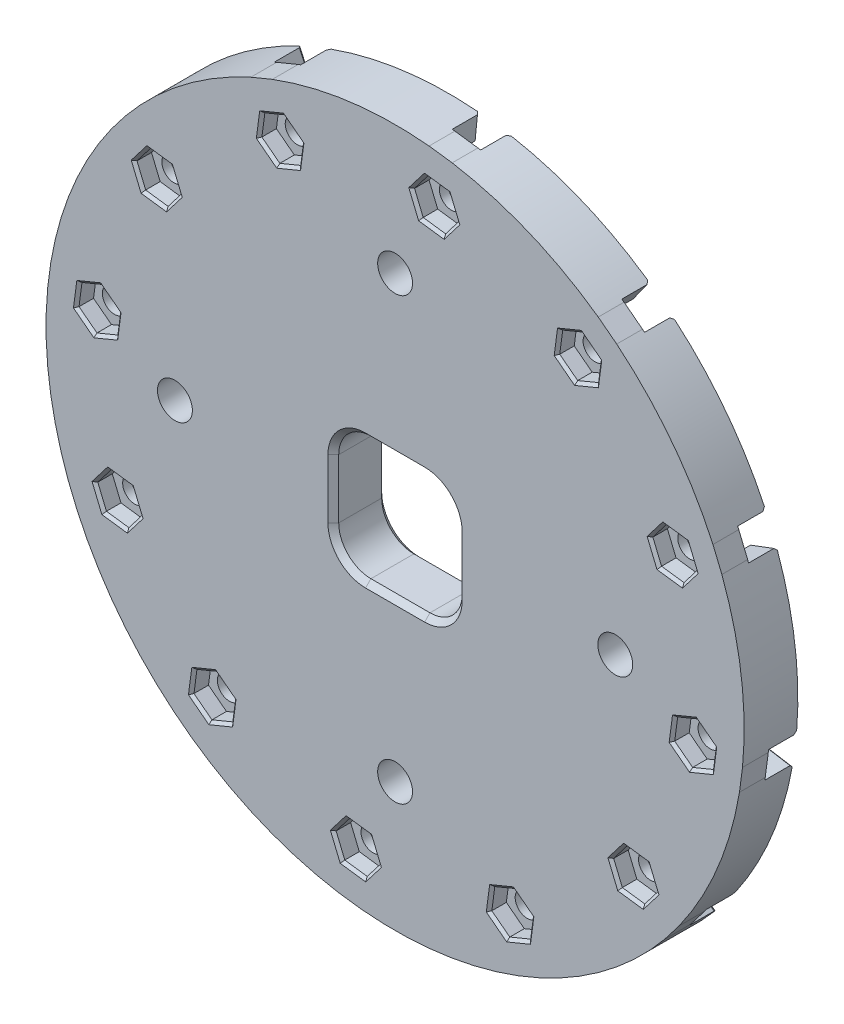
SolidWorks part; units mm, degrees
note: The reader was unsure of these and kept them because the rebuilt part matched: shared geometry of "Sketch4<7>".
material "ABS"
ref_plane "Front" through (0, 0, 0) normal (0, 0, 1) x (1, 0, 0)
ref_plane "Top" through (0, 0, 0) normal (0, 1, 0) x (1, 0, 0)
ref_plane "Right" through (0, 0, 0) normal (1, 0, 0) x (0, 0, -1)
sketch "Sketch1" plane through (0, 0, 0) normal (0, 0, 1) x (1, 0, 0)
  line L0 (-125.5954, 5.9057) -> (-58.2664, 51.1954)
  line L1 (-125.5954, -5.9057) -> (-58.2664, -51.1954)
  line L2 (0, 216.5) -> (0, -216.5) construction
  line L3 (-112.5, 5) -> (-102.5, 5)
  line L4 (-112.5, 5) -> (-112.5, -5)
  line L5 (-112.5, -5) -> (-102.5, -5)
  line L6 (-102.5, 5) -> (-102.5, -5)
  line L7 (-112.5, 5) -> (-102.5, -5) construction
  line L8 (-112.5, -5) -> (-102.5, 5) construction
  line L9 (216.5, 0) -> (-216.5, 0) construction
  line L10 (0, 0) -> (-153.0886, 153.0886) construction
  line L11 (0, 0) -> (153.0886, 153.0886) construction
  line L12 (0, 0) -> (153.0886, -153.0886) construction
  line L13 (0, 0) -> (-153.0886, -153.0886) construction
  line L14 (-5, 196.4364) -> (-5, 145.6348)
  line L15 (5, 196.4364) -> (5, 145.6348)
  line L16 (-5, -74.8331) -> (-5, -125.6348)
  line L17 (5, -74.8331) -> (5, -125.6348)
  line L18 (74.8331, 5) -> (125.6348, 5)
  line L19 (74.8331, -5) -> (125.6348, -5)
  line L22 (-142.437, 135.366) -> (-106.5149, 99.4438)
  line L23 (-49.8116, 56.8826) -> (-85.3017, 92.3727)
  line L24 (-49.8116, 56.8826) -> (-41.8605, 62.231)
  line L25 (-58.2664, -51.1954) -> (-92.3727, -85.3017)
  line L26 (-135.366, -142.437) -> (-99.4438, -106.5149)
  line L27 (-49.8116, -56.8826) -> (-41.8605, -62.231)
  line L28 (49.3795, -56.4506) -> (85.3017, -92.3727)
  line L29 (56.4506, -49.3795) -> (92.3727, -85.3017)
  line L30 (142.437, 135.366) -> (106.5149, 99.4438)
  line L31 (135.366, 142.437) -> (99.4438, 106.5149)
  line L32 (85.3017, 92.3727) -> (49.3795, 56.4506)
  line L33 (-11.5, 11.5) -> (11.5, 11.5)
  line L34 (-11.5, 11.5) -> (-11.5, -11.5)
  line L35 (-11.5, -11.5) -> (11.5, -11.5)
  line L36 (11.5, 11.5) -> (11.5, -11.5)
  line L37 (-11.5, 11.5) -> (11.5, -11.5) construction
  line L38 (-11.5, -11.5) -> (11.5, 11.5) construction
  line L39 (92.3727, 85.3017) -> (56.4506, 49.3795)
  line L40 (5, 125.6348) -> (5, 74.8331)
  line L41 (-5, 125.6348) -> (-5, 74.8331)
  line L42 (145.6348, 5) -> (196.4364, 5)
  line L43 (145.6348, -5) -> (196.4364, -5)
  line L44 (-99.4438, 106.5149) -> (-135.366, 142.437)
  line L45 (-92.3727, 85.3017) -> (-58.2664, 51.1954)
  line L46 (-145.6348, 5) -> (-196.4364, 5)
  line L47 (-145.6348, -5) -> (-196.4364, -5)
  line L48 (-106.5149, -99.4438) -> (-142.437, -135.366)
  line L49 (-85.3017, -92.3727) -> (-49.8116, -56.8826)
  line L50 (-5, -145.6348) -> (-5, -196.4364)
  line L51 (5, -145.6348) -> (5, -196.4364)
  line L52 (99.4438, -106.5149) -> (135.366, -142.437)
  line L53 (106.5149, -99.4438) -> (142.437, -135.366)
  line L54 (125.6348, 5) -> (145.6348, 5) construction
  line L55 (135.6348, 5) -> (135.6348, 23.3446) construction
  line L56 (74.8331, 2.5) -> (196.4364, 2.5) construction
  arc A0 (-41.8605, -62.231) -> (-5, -74.8331) centre (0, 0) ccw
  arc A2 (5, -74.8331) -> (49.3795, -56.4506) centre (0, 0) ccw
  circle A3 centre (0, 0) radius 216.5
  arc A4 (-5, 196.4364) -> (-135.366, 142.437) centre (0, 0) ccw
  arc A5 (-5, 74.8331) -> (-41.8605, 62.231) centre (0, 0) ccw
  arc A6 (5, -196.4364) -> (135.366, -142.437) centre (0, 0) ccw
  arc A7 (74.8331, 5) -> (56.4506, 49.3795) centre (0, 0) ccw
  arc A8 (196.4364, 5) -> (142.437, 135.366) centre (0, 0) ccw
  arc A9 (-196.4364, -5) -> (-142.437, -135.366) centre (0, 0) ccw
  arc A11 (-142.437, 135.366) -> (-196.4364, 5) centre (0, 0) ccw
  arc A12 (-135.366, -142.437) -> (-5, -196.4364) centre (0, 0) ccw
  arc A13 (56.4506, -49.3795) -> (74.8331, -5) centre (0, 0) ccw
  arc A14 (142.437, -135.366) -> (196.4364, -5) centre (0, 0) ccw
  arc A15 (49.3795, 56.4506) -> (5, 74.8331) centre (0, 0) ccw
  arc A16 (135.366, 142.437) -> (5, 196.4364) centre (0, 0) ccw
  circle A17 centre (0, 41) radius 3.25
  circle A18 centre (41, 0) radius 3.25
  circle A19 centre (0, -41) radius 3.25
  circle A20 centre (-41, 0) radius 3.25
  arc A21 (85.3017, 92.3727) -> (5, 125.6348) centre (0, 0) ccw
  arc A22 (99.4438, 106.5149) -> (5, 145.6348) centre (0, 0) ccw
  arc A23 (-5, 145.6348) -> (-99.4438, 106.5149) centre (0, 0) ccw
  arc A24 (-5, 125.6348) -> (-85.3017, 92.3727) centre (0, 0) ccw
  arc A25 (125.6348, 5) -> (92.3727, 85.3017) centre (0, 0) ccw
  arc A26 (145.6348, 5) -> (106.5149, 99.4438) centre (0, 0) ccw
  arc A27 (-106.5149, 99.4438) -> (-145.6348, 5) centre (0, 0) ccw
  arc A28 (-92.3727, 85.3017) -> (-125.5954, 5.9057) centre (0, 0) ccw
  arc A29 (-145.6348, -5) -> (-106.5149, -99.4438) centre (0, 0) ccw
  arc A30 (-125.5954, -5.9057) -> (-92.3727, -85.3017) centre (0, 0) ccw
  arc A31 (-85.3017, -92.3727) -> (-5, -125.6348) centre (0, 0) ccw
  arc A32 (-99.4438, -106.5149) -> (-5, -145.6348) centre (0, 0) ccw
  arc A33 (5, -125.6348) -> (85.3017, -92.3727) centre (0, 0) ccw
  arc A34 (5, -145.6348) -> (99.4438, -106.5149) centre (0, 0) ccw
  arc A35 (92.3727, -85.3017) -> (125.6348, -5) centre (0, 0) ccw
  arc A36 (106.5149, -99.4438) -> (145.6348, -5) centre (0, 0) ccw
  point P25 (0, 0)
  point P33 (-107.5, 0)
  point P68 (0, 0)
  point P105 (135.6348, 2.5)
  dimension "D1" = 150
  dimension "D6" = 433
  dimension "D9" = 20
  dimension "D19" = 6.5
  dimension "D3" = 107.5
  dimension "D4" = 10
  dimension "D5" = 10
  dimension "D7" = 45
  dimension "D8" = 4
  dimension "D10" = 5
  dimension "D11" = 10
  dimension "D12" = 5
  dimension "D13" = 10
  dimension "D14" = 10
  dimension "D15" = 10
  dimension "D16" = 10
  dimension "D17" = 10
  dimension "D18" = 23
  dimension "D20" = 29.5
  dimension "D22" = 10
  dimension "D23" = 2.5
  dimension "D24" = 33.927
  dimension "D25" = 33.927
  dimension "D21" = 4
extrude "Boss-Extrude1" add sketch "Sketch1" along normal blind 10
sketch "Sketch3" plane through (0, 0, 0) normal (0, 1, 0) x (1, 0, 0)
  line L0 (-216.5, -10) -> (-221.5, -10)
  line L1 (-221.5, -10) -> (-221.5, 5)
  line L2 (-221.5, 5) -> (-211.5, 5)
  line L3 (-211.5, 5) -> (-211.5, 2)
  line L4 (-211.5, 2) -> (-216.5, 2)
  line L6 (-216.5, 2) -> (-216.5, -10)
  line L7 (216.5, 0) -> (-216.5, 0) construction
  line L8 (0, 88.3927) -> (0, -66.2884) construction
  dimension "D1" = 2
  dimension "D2" = 3
  dimension "D3" = 5
  dimension "D4" = 10
revolve "Revolve1" add sketch "Sketch3" angle 360 about L8
sketch "Sketch4" plane through (0, 0, 10) normal (0, 0, 1) x (1, 0, 0)
  line L0 (-83.9188, 109.3651) -> (-79.952, 112.4089)
  line L1 (84.7644, 204.6393) -> (24.8744, 60.0522)
  line L2 (5, 125.6348) -> (5, 74.8331) construction
  line L3 (-134.8407, 175.7278) -> (-39.5695, 51.568)
  line L4 (-219.605, -28.9116) -> (-64.4439, -8.4842)
  line L5 (39.5695, -51.568) -> (134.8407, -175.7278)
  line L6 (64.4439, 8.4842) -> (219.605, 28.9116)
  line L7 (-24.8744, -60.0522) -> (-84.7644, -204.6393)
  line L8 (24.8744, 60.0522) -> (-24.8744, -60.0522) construction
  line L9 (-26.8634, 59.1892) -> (-24.797, 54.6361)
  line L10 (-24.797, 54.6361) -> (-29.397, 52.9082)
  line L11 (-29.397, 52.9082) -> (-25.5115, 45.9151)
  line L12 (-25.5115, 45.9151) -> (-14.2779, 50.135)
  line L13 (-14.2779, 50.135) -> (-16.4525, 57.7708)
  line L14 (-16.4525, 57.7708) -> (-21.0525, 56.0428)
  line L15 (-21.0525, 56.0428) -> (-22.8577, 60.8484)
  line L16 (-22.8577, 60.8484) -> (0, 0) construction
  line L17 (-26.8634, 59.1892) -> (0, 0) construction
  line L18 (0, 0) -> (-16.4525, 57.7708) construction
  line L19 (-29.397, 52.9082) -> (0, 0) construction
  line L20 (-26.8634, 59.1892) -> (-22.8577, 60.8484)
  line L21 (-24.8606, 60.0188) -> (0, 0) construction
  line L22 (6.3302, 64.691) -> (10.6288, 64.1251)
  line L23 (9.7894, 59.0607) -> (10.6288, 64.1251)
  line L24 (14.6371, 58.2572) -> (9.7894, 59.0607)
  line L25 (12.7024, 50.5571) -> (14.6371, 58.2572)
  line L26 (0.864, 52.5194) -> (12.7024, 50.5571)
  line L27 (0.9955, 60.5183) -> (0.864, 52.5194)
  line L28 (5.8432, 59.7148) -> (0.9955, 60.5183)
  line L29 (6.3302, 64.691) -> (5.8432, 59.7148)
  line L30 (37.8276, 52.859) -> (41.2674, 50.2196)
  line L31 (38.0082, 46.2534) -> (41.2674, 50.2196)
  line L32 (41.8047, 43.1337) -> (38.0082, 46.2534)
  line L33 (36.2792, 37.4326) -> (41.8047, 43.1337)
  line L34 (27.0079, 45.0511) -> (36.2792, 37.4326)
  line L35 (31.1213, 51.9126) -> (27.0079, 45.0511)
  line L36 (34.9178, 48.7929) -> (31.1213, 51.9126)
  line L37 (37.8276, 52.859) -> (34.9178, 48.7929)
  line L38 (59.1892, 26.8634) -> (60.8484, 22.8577)
  line L39 (56.0428, 21.0525) -> (60.8484, 22.8577)
  line L40 (57.7708, 16.4525) -> (56.0428, 21.0525)
  line L41 (50.135, 14.2779) -> (57.7708, 16.4525)
  line L42 (45.9151, 25.5115) -> (50.135, 14.2779)
  line L43 (52.9082, 29.397) -> (45.9151, 25.5115)
  line L44 (54.6361, 24.797) -> (52.9082, 29.397)
  line L45 (59.1892, 26.8634) -> (54.6361, 24.797)
  line L46 (64.691, -6.3302) -> (64.1251, -10.6288)
  line L47 (59.0607, -9.7894) -> (64.1251, -10.6288)
  line L48 (58.2572, -14.6371) -> (59.0607, -9.7894)
  line L49 (50.5571, -12.7024) -> (58.2572, -14.6371)
  line L50 (52.5194, -0.864) -> (50.5571, -12.7024)
  line L51 (60.5183, -0.9955) -> (52.5194, -0.864)
  line L52 (59.7148, -5.8432) -> (60.5183, -0.9955)
  line L53 (64.691, -6.3302) -> (59.7148, -5.8432)
  line L54 (52.859, -37.8276) -> (50.2196, -41.2674)
  line L55 (46.2534, -38.0082) -> (50.2196, -41.2674)
  line L56 (43.1337, -41.8047) -> (46.2534, -38.0082)
  line L57 (37.4326, -36.2792) -> (43.1337, -41.8047)
  line L58 (45.0511, -27.0079) -> (37.4326, -36.2792)
  line L59 (51.9126, -31.1213) -> (45.0511, -27.0079)
  line L60 (48.7929, -34.9178) -> (51.9126, -31.1213)
  line L61 (52.859, -37.8276) -> (48.7929, -34.9178)
  line L62 (26.8634, -59.1892) -> (22.8577, -60.8484)
  line L63 (21.0525, -56.0428) -> (22.8577, -60.8484)
  line L64 (16.4525, -57.7708) -> (21.0525, -56.0428)
  line L65 (14.2779, -50.135) -> (16.4525, -57.7708)
  line L66 (25.5115, -45.9151) -> (14.2779, -50.135)
  line L67 (29.397, -52.9082) -> (25.5115, -45.9151)
  line L68 (24.797, -54.6361) -> (29.397, -52.9082)
  line L69 (26.8634, -59.1892) -> (24.797, -54.6361)
  line L70 (-6.3302, -64.691) -> (-10.6288, -64.1251)
  line L71 (-9.7894, -59.0607) -> (-10.6288, -64.1251)
  line L72 (-14.6371, -58.2572) -> (-9.7894, -59.0607)
  line L73 (-12.7024, -50.5571) -> (-14.6371, -58.2572)
  line L74 (-0.864, -52.5194) -> (-12.7024, -50.5571)
  line L75 (-0.9955, -60.5183) -> (-0.864, -52.5194)
  line L76 (-5.8432, -59.7148) -> (-0.9955, -60.5183)
  line L77 (-6.3302, -64.691) -> (-5.8432, -59.7148)
  line L78 (-37.8276, -52.859) -> (-41.2674, -50.2196)
  line L79 (-38.0082, -46.2534) -> (-41.2674, -50.2196)
  line L80 (-41.8047, -43.1337) -> (-38.0082, -46.2534)
  line L81 (-36.2792, -37.4326) -> (-41.8047, -43.1337)
  line L82 (-27.0079, -45.0511) -> (-36.2792, -37.4326)
  line L83 (-31.1213, -51.9126) -> (-27.0079, -45.0511)
  line L84 (-34.9178, -48.7929) -> (-31.1213, -51.9126)
  line L85 (-37.8276, -52.859) -> (-34.9178, -48.7929)
  line L86 (-59.1892, -26.8634) -> (-60.8484, -22.8577)
  line L87 (-56.0428, -21.0525) -> (-60.8484, -22.8577)
  line L88 (-57.7708, -16.4525) -> (-56.0428, -21.0525)
  line L89 (-50.135, -14.2779) -> (-57.7708, -16.4525)
  line L90 (-45.9151, -25.5115) -> (-50.135, -14.2779)
  line L91 (-52.9082, -29.397) -> (-45.9151, -25.5115)
  line L92 (-54.6361, -24.797) -> (-52.9082, -29.397)
  line L93 (-59.1892, -26.8634) -> (-54.6361, -24.797)
  line L94 (-64.691, 6.3302) -> (-64.1251, 10.6288)
  line L95 (-59.0607, 9.7894) -> (-64.1251, 10.6288)
  line L96 (-58.2572, 14.6371) -> (-59.0607, 9.7894)
  line L97 (-50.5571, 12.7024) -> (-58.2572, 14.6371)
  line L98 (-52.5194, 0.864) -> (-50.5571, 12.7024)
  line L99 (-60.5183, 0.9955) -> (-52.5194, 0.864)
  line L100 (-59.7148, 5.8432) -> (-60.5183, 0.9955)
  line L101 (-64.691, 6.3302) -> (-59.7148, 5.8432)
  line L102 (-52.859, 37.8276) -> (-50.2196, 41.2674)
  line L103 (-46.2534, 38.0082) -> (-50.2196, 41.2674)
  line L104 (-43.1337, 41.8047) -> (-46.2534, 38.0082)
  line L105 (-37.4326, 36.2792) -> (-43.1337, 41.8047)
  line L106 (-45.0511, 27.0079) -> (-37.4326, 36.2792)
  line L107 (-51.9126, 31.1213) -> (-45.0511, 27.0079)
  line L108 (-48.7929, 34.9178) -> (-51.9126, 31.1213)
  line L109 (-52.859, 37.8276) -> (-48.7929, 34.9178)
  line L110 (-128.753, 167.7942) -> (-124.7863, 170.838)
  line L111 (-124.7863, 170.838) -> (-126.9169, 173.6148)
  line L112 (-126.9169, 173.6148) -> (-122.9502, 176.6586)
  line L113 (-122.9502, 176.6586) -> (-115.645, 167.1383)
  line L114 (-115.645, 167.1383) -> (-119.6118, 164.0945)
  line L115 (-119.6118, 164.0945) -> (-121.7425, 166.8713)
  line L116 (-121.7425, 166.8713) -> (-125.7092, 163.8275)
  line L117 (-125.7092, 163.8275) -> (-128.753, 167.7942)
  line L118 (-124.7863, 170.838) -> (-121.7425, 166.8713) construction
  line L119 (-134.8407, 175.7278) -> (-118.7343, 188.0866) construction
  line L120 (79.0241, 190.7811) -> (80.9375, 195.4005)
  line L121 (80.9375, 195.4005) -> (85.5569, 193.4871)
  line L122 (85.5569, 193.4871) -> (86.8963, 196.7207)
  line L123 (86.8963, 196.7207) -> (91.5157, 194.8073)
  line L124 (91.5157, 194.8073) -> (86.9235, 183.7207)
  line L125 (86.9235, 183.7207) -> (82.3041, 185.6341)
  line L126 (82.3041, 185.6341) -> (83.6435, 188.8677)
  line L127 (83.6435, 188.8677) -> (79.0241, 190.7811)
  line L128 (204.7334, 26.9537) -> (209.6906, 27.6063)
  line L129 (209.6906, 27.6063) -> (210.3432, 22.6491)
  line L130 (210.3432, 22.6491) -> (213.8133, 23.1059)
  line L131 (213.8133, 23.1059) -> (214.4659, 18.1487)
  line L132 (214.4659, 18.1487) -> (202.5686, 16.5824)
  line L133 (202.5686, 16.5824) -> (201.9159, 21.5396)
  line L134 (201.9159, 21.5396) -> (205.386, 21.9964)
  line L135 (205.386, 21.9964) -> (204.7334, 26.9537)
  line L136 (125.7092, -163.8275) -> (128.753, -167.7942)
  line L137 (128.753, -167.7942) -> (124.7863, -170.838)
  line L138 (124.7863, -170.838) -> (126.9169, -173.6148)
  line L139 (126.9169, -173.6148) -> (122.9502, -176.6586)
  line L140 (122.9502, -176.6586) -> (115.645, -167.1383)
  line L141 (115.645, -167.1383) -> (119.6118, -164.0945)
  line L142 (119.6118, -164.0945) -> (121.7425, -166.8713)
  line L143 (121.7425, -166.8713) -> (125.7092, -163.8275)
  line L144 (-79.0241, -190.7811) -> (-80.9375, -195.4005)
  line L145 (-80.9375, -195.4005) -> (-85.5569, -193.4871)
  line L146 (-85.5569, -193.4871) -> (-86.8963, -196.7207)
  line L147 (-86.8963, -196.7207) -> (-91.5157, -194.8073)
  line L148 (-91.5157, -194.8073) -> (-86.9235, -183.7207)
  line L149 (-86.9235, -183.7207) -> (-82.3041, -185.6341)
  line L150 (-82.3041, -185.6341) -> (-83.6435, -188.8677)
  line L151 (-83.6435, -188.8677) -> (-79.0241, -190.7811)
  line L152 (-204.7334, -26.9537) -> (-209.6906, -27.6063)
  line L153 (-209.6906, -27.6063) -> (-210.3432, -22.6491)
  line L154 (-210.3432, -22.6491) -> (-213.8133, -23.1059)
  line L155 (-213.8133, -23.1059) -> (-214.4659, -18.1487)
  line L156 (-214.4659, -18.1487) -> (-202.5686, -16.5824)
  line L157 (-202.5686, -16.5824) -> (-201.9159, -21.5396)
  line L158 (-201.9159, -21.5396) -> (-205.386, -21.9964)
  line L159 (-205.386, -21.9964) -> (-204.7334, -26.9537)
  line L160 (-79.952, 112.4089) -> (-82.0827, 115.1856)
  line L161 (-82.0827, 115.1856) -> (-78.1159, 118.2294)
  line L162 (-78.1159, 118.2294) -> (-70.8108, 108.7092)
  line L163 (-70.8108, 108.7092) -> (-74.7775, 105.6654)
  line L164 (-74.7775, 105.6654) -> (-76.9082, 108.4421)
  line L165 (-76.9082, 108.4421) -> (-80.875, 105.3983)
  line L166 (-83.9188, 109.3651) -> (-80.875, 105.3983)
  line L167 (52.7535, 127.3583) -> (50.8401, 122.7389)
  line L168 (55.4595, 120.8255) -> (50.8401, 122.7389)
  line L169 (54.1201, 117.5919) -> (55.4595, 120.8255)
  line L170 (58.7395, 115.6785) -> (54.1201, 117.5919)
  line L171 (63.3317, 126.7651) -> (58.7395, 115.6785)
  line L172 (58.7123, 128.6785) -> (63.3317, 126.7651)
  line L173 (57.3729, 125.4449) -> (58.7123, 128.6785)
  line L174 (52.7535, 127.3583) -> (57.3729, 125.4449)
  line L175 (136.6723, 17.9933) -> (131.7151, 17.3406)
  line L176 (132.3677, 12.3834) -> (131.7151, 17.3406)
  line L177 (128.8977, 11.9266) -> (132.3677, 12.3834)
  line L178 (129.5503, 6.9693) -> (128.8977, 11.9266)
  line L179 (141.4476, 8.5356) -> (129.5503, 6.9693)
  line L180 (140.795, 13.4929) -> (141.4476, 8.5356)
  line L181 (137.325, 13.036) -> (140.795, 13.4929)
  line L182 (136.6723, 17.9933) -> (137.325, 13.036)
  line L183 (83.9188, -109.3651) -> (80.875, -105.3983)
  line L184 (76.9082, -108.4421) -> (80.875, -105.3983)
  line L185 (74.7775, -105.6654) -> (76.9082, -108.4421)
  line L186 (70.8108, -108.7092) -> (74.7775, -105.6654)
  line L187 (78.1159, -118.2294) -> (70.8108, -108.7092)
  line L188 (82.0827, -115.1856) -> (78.1159, -118.2294)
  line L189 (79.952, -112.4089) -> (82.0827, -115.1856)
  line L190 (83.9188, -109.3651) -> (79.952, -112.4089)
  line L191 (-52.7535, -127.3583) -> (-50.8401, -122.7389)
  line L192 (-55.4595, -120.8255) -> (-50.8401, -122.7389)
  line L193 (-54.1201, -117.5919) -> (-55.4595, -120.8255)
  line L194 (-58.7395, -115.6785) -> (-54.1201, -117.5919)
  line L195 (-63.3317, -126.7651) -> (-58.7395, -115.6785)
  line L196 (-58.7123, -128.6785) -> (-63.3317, -126.7651)
  line L197 (-57.3729, -125.4449) -> (-58.7123, -128.6785)
  line L198 (-52.7535, -127.3583) -> (-57.3729, -125.4449)
  line L199 (-136.6723, -17.9933) -> (-131.7151, -17.3406)
  line L200 (-132.3677, -12.3834) -> (-131.7151, -17.3406)
  line L201 (-128.8977, -11.9266) -> (-132.3677, -12.3834)
  line L202 (-129.5503, -6.9693) -> (-128.8977, -11.9266)
  line L203 (-141.4476, -8.5356) -> (-129.5503, -6.9693)
  line L204 (-140.795, -13.4929) -> (-141.4476, -8.5356)
  line L205 (-137.325, -13.036) -> (-140.795, -13.4929)
  line L206 (-136.6723, -17.9933) -> (-137.325, -13.036)
  circle A0 centre (0, 0) radius 65
  circle A1 centre (0, 0) radius 221.5
  circle A2 centre (0, 0) radius 221.5 construction
  arc A3 (49.3795, 56.4506) -> (5, 74.8331) centre (0, 0) ccw construction
  arc A7 (-5, 145.6348) -> (-99.4438, 106.5149) centre (0, 0) ccw construction
  point P125 (0, 0)
  point P132 (-123.2644, 168.8547)
  point P176 (0, 0)
  point P183 (-74.4633, 113.4693)
  point P228 (0, 0)
  dimension "D14" = 12.5
  dimension "D16" = 10
  dimension "D1" = 22.5
  dimension "D2" = 60
  dimension "D3" = 60
  dimension "D4" = 12
  dimension "D5" = 5
  dimension "D6" = 8
  dimension "D7" = 4
  dimension "D8" = 22.5
  dimension "D10" = 5
  dimension "D11" = 5
  dimension "D12" = 12
  dimension "D13" = 5
  dimension "D17" = 12
  dimension "D18" = 5
  dimension "D19" = 5
  dimension "D20" = 5
  dimension "D21" = 10
  dimension "D9" = 12
  dimension "D15" = 6
  dimension "D22" = 6
extrude "Cut-Extrude4" cut sketch "Sketch4" against normal through all contours L159 L158 L157 L156 L155 L154 L153 L4 | L206 L4 L200 L201 L202 L203 L204 L205 | L3 A1 L4 L153 L154 L155 L156 L157 L158 L159 L206 L205 L204 L203 L202 L201 L200 A0 | L165 L164 L163 L162 L161 L160 L0 L3 | L116 L115 L114 L113 L112 L111 L110 L3 | L1 A1 L3 L110 L111 L112 L113 L114 L115 L116 L0 L160 L161 L162 L163 L164 L165 A0 | L174 L1 L168 L169 L170 L171 L172 L173 | L127 L126 L125 L124 L123 L122 L121 L1 | L6 A1 L1 L121 L122 L123 L124 L125 L126 L127 L174 L173 L172 L171 L170 L169 L168 A0 | L182 L6 L176 L177 L178 L179 L180 L181 | L135 L134 L133 L132 L131 L130 L129 L6 | L5 A1 L6 L129 L130 L131 L132 L133 L134 L135 L182 L181 L180 L179 L178 L177 L176 A0 | L46 L53 L52 L51 L50 L49 L48 L47 | L38 L45 L44 L43 L42 L41 L40 L39 | L54 L61 L60 L59 L58 L57 L56 L55 | L7 A1 L5 L137 L138 L139 L140 L141 L142 L143 L190 L189 L188 L187 L186 L185 L184 A0 | L190 L5 L184 L185 L186 L187 L188 L189 | L143 L142 L141 L140 L139 L138 L137 L5 | L4 A1 L7 L145 L146 L147 L148 L149 L150 L151 L198 L197 L196 L195 L194 L193 L192 A0 | L198 L7 L192 L193 L194 L195 L196 L197 | L151 L150 L149 L148 L147 L146 L145 L7 | L30 L37 L36 L35 L34 L33 L32 L31 | L22 L29 L28 L27 L26 L25 L24 L23 | L20 L9 L10 L11 L12 L13 L14 L15 | L102 L109 L108 L107 L106 L105 L104 L103 | L94 L101 L100 L99 L98 L97 L96 L95 | L86 L93 L92 L91 L90 L89 L88 L87 | L78 L85 L84 L83 L82 L81 L80 L79 | L70 L77 L76 L75 L74 L73 L72 L71 | L62 L69 L68 L67 L66 L65 L64 L63
extrude "Boss-Extrude2" add sketch "Sketch4<7>" against normal blind 4.8 contours L86 L93 L92 L91 L90 L89 L88 L87 | L78 L85 L84 L83 L82 L81 L80 L79 | L70 L77 L76 L75 L74 L73 L72 L71 | L62 L69 L68 L67 L66 L65 L64 L63 | L54 L61 L60 L59 L58 L57 L56 L55 | L46 L53 L52 L51 L50 L49 L48 L47 | L38 L45 L44 L43 L42 L41 L40 L39 | L30 L37 L36 L35 L34 L33 L32 L31 | L22 L29 L28 L27 L26 L25 L24 L23 | L20 L9 L10 L11 L12 L13 L14 L15 | L102 L109 L108 L107 L106 L105 L104 L103 | L94 L101 L100 L99 L98 L97 L96 L95
sketch "Sketch4<7>" plane through (0, 0, 10) normal (0, 0, 1) x (1, 0, 0) same geometry as "Sketch4"
sketch "Sketch5" plane through (0, 0, 0) normal (0, 0, -1) x (-1, 0, 0)
  line L0 (-13.6697, 54.4072) -> (-0.9297, 56.5188) construction
  line L1 (-12.7024, 50.5571) -> (-14.6371, 58.2572) construction
  line L2 (-0.9955, 60.5183) -> (-0.864, 52.5194) construction
  line L3 (-7.2997, 55.463) -> (-6.7832, 51.5383) construction
  line L4 (-0.864, 52.5194) -> (-12.7024, 50.5571) construction
  circle A0 centre (-7.2997, 55.463) radius 2.25
  circle A1 centre (21.4097, 51.6822) radius 2.25
  circle A2 centre (44.3825, 34.0533) radius 2.25
  circle A3 centre (55.463, 7.2997) radius 2.25
  circle A4 centre (51.6822, -21.4097) radius 2.25
  circle A5 centre (34.0533, -44.3825) radius 2.25
  circle A6 centre (7.2997, -55.463) radius 2.25
  circle A7 centre (-21.4097, -51.6822) radius 2.25
  circle A8 centre (-44.3825, -34.0533) radius 2.25
  circle A9 centre (-55.463, -7.2997) radius 2.25
  circle A10 centre (-51.6822, 21.4097) radius 2.25
  circle A11 centre (-34.0533, 44.3825) radius 2.25
  point P36 (0, 0)
  dimension "D1" = 4.5
  dimension "D2" = 12
extrude "Cut-Extrude5" cut sketch "Sketch5" against normal through all
sketch "Sketch6" plane through (0, 0, 10) normal (0, 0, 1) x (1, 0, 0)
  line L0 (7.2997, 55.463) -> (8.4795, 64.4081) construction
  line L1 (8.9117, 51.5688) -> (11.4782, 54.9119)
  line L2 (11.4782, 54.9119) -> (9.8662, 58.8061)
  line L3 (9.8662, 58.8061) -> (5.6878, 59.3572)
  line L4 (5.6878, 59.3572) -> (3.1213, 56.0141)
  line L5 (3.1213, 56.0141) -> (4.7333, 52.1199)
  line L6 (4.7333, 52.1199) -> (8.9117, 51.5688)
  line L7 (6.3302, 64.691) -> (10.6288, 64.1251) construction
  circle A0 centre (7.2997, 55.463) radius 3.65 construction
  dimension "D1" = 7.3
extrude "Cut-Extrude6" cut sketch "Sketch6" against normal blind 3.2
chamfer "Chamfer1" distance 0.5 angle 45 6 edges at (3.9273, 54.067, 10) (6.8225, 51.8443, 10) (10.195, 53.2404, 10) (10.6722, 56.859, 10) (7.777, 59.0817, 10) (4.4045, 57.6857, 10)
pattern_circular "CirPattern1" count 12 over 360 about axis through (0, 0, 0) along (0, 0, 1) of "Chamfer1", "Cut-Extrude6"
sketch "Sketch7" plane through (0, 0, 0) normal (0, 0, -1) x (-1, 0, 0)
  line L0 (-34.8222, 49.5186) -> (-37.7218, 53.5704)
  line L1 (-34.8222, 49.5186) -> (-30.9907, 52.6671)
  line L2 (-30.9907, 52.6671) -> (-26.3574, 44.9385)
  line L3 (-26.3574, 44.9385) -> (-36.3177, 36.7538)
  line L4 (-36.3177, 36.7538) -> (-42.5414, 43.1754)
  line L5 (-42.5414, 43.1754) -> (-38.712, 46.3223)
  line L6 (-38.712, 46.3223) -> (-41.9819, 50.3015)
  line L8 (-37.8276, 52.859) -> (-34.9178, 48.7929) construction
  line L9 (-38.0082, 46.2534) -> (-41.2674, 50.2196) construction
  line L10 (-41.8047, 43.1337) -> (-38.0082, 46.2534) construction
  line L11 (-31.1213, 51.9126) -> (-27.0079, 45.0511) construction
  line L12 (-36.2792, 37.4326) -> (-41.8047, 43.1337) construction
  line L13 (-27.0079, 45.0511) -> (-36.2792, 37.4326) construction
  line L14 (-38.0082, 46.2534) -> (-41.2674, 50.2196) construction
  line L15 (-34.9178, 48.7929) -> (-31.1213, 51.9126) construction
  line L16 (-41.8047, 43.1337) -> (-38.0082, 46.2534) construction
  line L17 (-36.2792, 37.4326) -> (-41.8047, 43.1337) construction
  line L18 (-31.1213, 51.9126) -> (-27.0079, 45.0511) construction
  line L19 (-27.0079, 45.0511) -> (-36.2792, 37.4326) construction
  line L21 (-37.7218, 53.5704) -> (-41.9819, 50.3015)
  dimension "D1" = 0.5
  dimension "D2" = 0.5
  dimension "D3" = 0.5
  dimension "D4" = 0.5
  dimension "D5" = 0.5
  dimension "D6" = 0.5
  dimension "D7" = 0.5
  dimension "D8" = 0.5
  dimension "D9" = 0.5
extrude "Cut-Extrude8" cut sketch "Sketch7" against normal up to surface (5.2 mm away) up to face at (36.3033, 44.3825, 5.2)
chamfer "Chamfer2" distance 0.5 angle 45 7 edges at (36.1211, 51.3335, 0) (32.9065, 51.0929, 0) (40.1822, 48.1114, 0) (40.6267, 44.7488, 0) (39.4295, 39.9646, 0) (31.3375, 40.8462, 0) (28.674, 48.8028, 0)
pattern_circular "CirPattern2" count 12 over 360 about axis through (0, 0, 0) along (0, 0, 1) of "Chamfer2", "Cut-Extrude8"
fillet "Скругление1" radius 6 4 edges at (11.5, -11.5, 5) (-11.5, -11.5, 5) (11.5, 11.5, 5) (-11.5, 11.5, 5)
chamfer "Chamfer3" distance 1 angle 45 16 edges at (0, -11.5, 10) (0, -11.5, 0) (-11.5, 0, 10) (-11.5, 0, 0) (11.5, 0, 0) (11.5, 0, 10) (0, 11.5, 0) (0, 11.5, 10) (9.7426, -9.7426, 10) (9.7426, -9.7426, 0) (-9.7426, -9.7426, 10) (-9.7426, -9.7426, 0) (9.7426, 9.7426, 10) (9.7426, 9.7426, 0) (-9.7426, 9.7426, 10) (-9.7426, 9.7426, 0)
